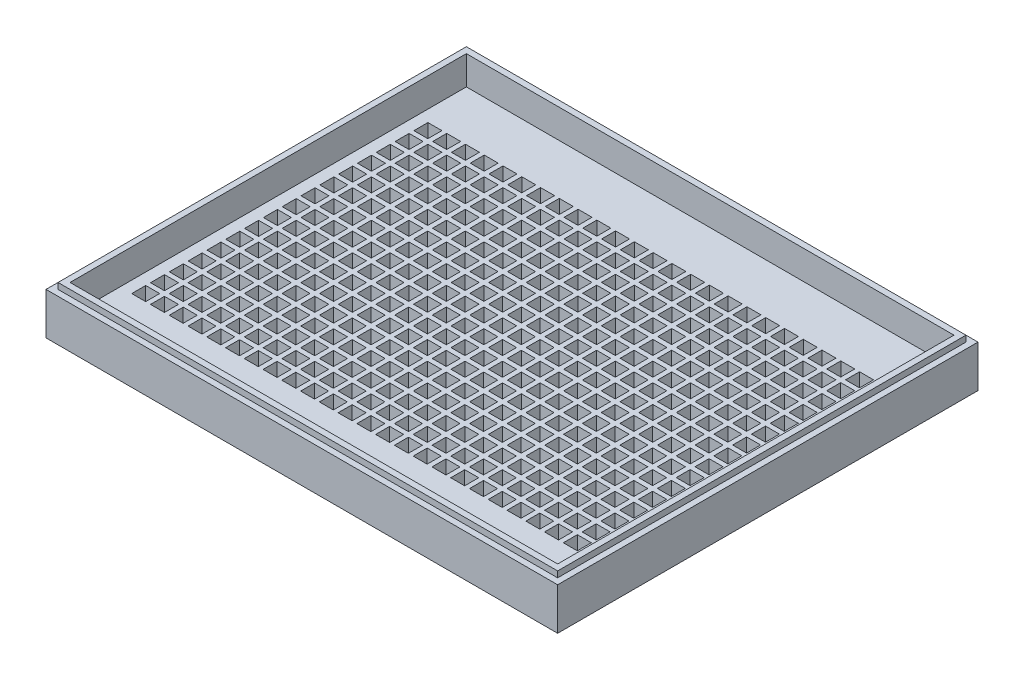
SolidWorks part; units mm, degrees
ref_plane "前视基准面" through (0, 0, 0) normal (0, 0, 1) x (1, 0, 0)
ref_plane "上视基准面" through (0, 0, 0) normal (0, 1, 0) x (1, 0, 0)
ref_plane "右视基准面" through (0, 0, 0) normal (1, 0, 0) x (0, 0, -1)
other "Configuration Table"
sketch "草图1" plane through (0, 0, 0) normal (0, 1, 0) x (1, 0, 0)
  line L1 (-42.6, 35) -> (42.6, 35)
  line L2 (-42.6, 35) -> (-42.6, -35)
  line L3 (-42.6, -35) -> (42.6, -35)
  line L4 (42.6, 35) -> (42.6, -35)
  line L5 (-42.6, 35) -> (42.6, -35) construction
  line L6 (-42.6, -35) -> (42.6, 35) construction
  point P0 (0, 0)
  dimension "D1" = 70
  dimension "D2" = 85.2
extrude "凸台-拉伸1" add sketch "草图1" along normal blind 8
sketch "草图2" plane through (0, 8, 0) normal (0, 1, 0) x (1, 0, 0)
  line L0 (-41.6, 34) -> (41.6, 34)
  line L5 (-42.6, 35) -> (42.6, 35)
  line L6 (-42.6, 35) -> (-42.6, -35)
  line L7 (-42.6, -35) -> (42.6, -35)
  line L8 (42.6, 35) -> (42.6, -35)
  line L9 (-42.6, 35) -> (42.6, -35) construction
  line L10 (-42.6, -35) -> (42.6, 35) construction
  line L11 (41.6, 34) -> (41.6, -34)
  line L12 (-41.6, -34) -> (41.6, -34)
  line L13 (-41.6, 34) -> (-41.6, -34)
  point P0 (0, 0)
  dimension "D1" = 1
extrude "切除-拉伸1" cut sketch "草图2" against normal blind 1
sketch "草图3" plane through (0, 8, 0) normal (0, 1, 0) x (1, 0, 0)
  line L0 (-41.6, 34) -> (-41.6, -34) construction
  line L1 (40.6, 33) -> (-40.6, 33)
  line L2 (40.6, 33) -> (40.6, -33)
  line L3 (40.6, -33) -> (-40.6, -33)
  line L4 (-40.6, 33) -> (-40.6, -33)
  line L5 (40.6, 33) -> (-40.6, -33) construction
  line L6 (40.6, -33) -> (-40.6, 33) construction
  line L7 (41.6, 34) -> (-41.6, 34) construction
  point P0 (0, 0)
  dimension "D1" = 1
  dimension "D2" = 1
extrude "切除-拉伸2" cut sketch "草图3" against normal offset from surface (7.8 mm away) 0.2 up to face at (0, 0, 0)
sketch "草图4" plane through (0, 0.2, 0) normal (0, 1, 0) x (1, 0, 0)
  line L0 (-40.6, -33) -> (-40.6, 33) construction
  line L1 (-40.6, 33) -> (40.6, 33) construction
  line L2 (40.6, -33) -> (-40.6, -33) construction
  circle A0 centre (-33.2, 29) radius 2.4
  circle A1 centre (32.7, 29) radius 2.4
  circle A2 centre (-33.2, -29) radius 2.4
  circle A3 centre (12.2, -29) radius 2.4
  dimension "D1" = 4.8
  dimension "D2" = 7.4
  dimension "D3" = 4
  dimension "D4" = 65.9
  dimension "D5" = 4
  dimension "D6" = 45.4
sketch "草图5" plane through (0, 0.2, 0) normal (0, 1, 0) x (1, 0, 0)
  line L1 (-39.46, 25.46) -> (38.94, 25.46)
  line L2 (-39.46, 25.46) -> (-39.46, 24.66)
  line L3 (-39.46, 24.66) -> (38.94, 24.66)
  line L4 (38.94, 25.46) -> (38.94, 24.66)
  line L5 (-40.6, -33) -> (-40.6, 33) construction
  line L6 (-40.6, 33) -> (40.6, 33) construction
  dimension "D1" = 0.8
  dimension "D2" = 78.4
  dimension "D3" = 1.14
  dimension "D4" = 7.54
extrude "凸台-拉伸3" add sketch "草图5" along normal blind 3
pattern_linear "阵列(线性)1" count 17 spacing 3.133 along (0, 0, 1) of "凸台-拉伸3"
sketch "草图6" plane through (0, 0.2, 0) normal (0, 1, 0) x (1, 0, 0)
  line L0 (-39.46, -25.468) -> (38.94, -25.468) construction
  line L1 (-39.46, 25.46) -> (-38.66, 25.46)
  line L2 (-39.46, 25.46) -> (-39.46, -25.468)
  line L3 (-39.46, -25.468) -> (-38.66, -25.468)
  line L4 (-38.66, 25.46) -> (-38.66, -25.468)
  dimension "D1" = 0.8
extrude "凸台-拉伸4" add sketch "草图6" along normal blind 3
pattern_linear "阵列(线性)2" count 26 spacing 3.125 along (1, 0, 0) of "凸台-拉伸4"
sketch "草图7" plane through (0, 0.2, 0) normal (0, 1, 0) x (1, 0, 0)
  line L0 (-39.46, -25.468) -> (39.465, -25.468) construction
  line L1 (-39.46, 25.46) -> (-39.46, -25.468) construction
  line L2 (39.465, -25.468) -> (39.465, 25.46) construction
  line L3 (39.465, 25.46) -> (-39.46, 25.46) construction
  line L4 (40.6, -33) -> (-40.6, -33) construction
  line L5 (40.6, 33) -> (40.6, -33) construction
  line L6 (-40.6, -33) -> (-40.6, 33) construction
  line L7 (-40.6, 33) -> (40.6, 33) construction
  line L8 (-39.46, -25.468) -> (39.465, -25.468)
  line L9 (-39.46, 25.46) -> (-39.46, -25.468)
  line L10 (39.465, -25.468) -> (39.465, 25.46)
  line L11 (39.465, 25.46) -> (-39.46, 25.46)
  line L12 (40.6, -33) -> (-40.6, -33)
  line L13 (40.6, 33) -> (40.6, -33)
  line L14 (-40.6, -33) -> (-40.6, 33)
  line L15 (-40.6, 33) -> (40.6, 33)
extrude "凸台-拉伸5" add sketch "草图7" along normal blind 3
